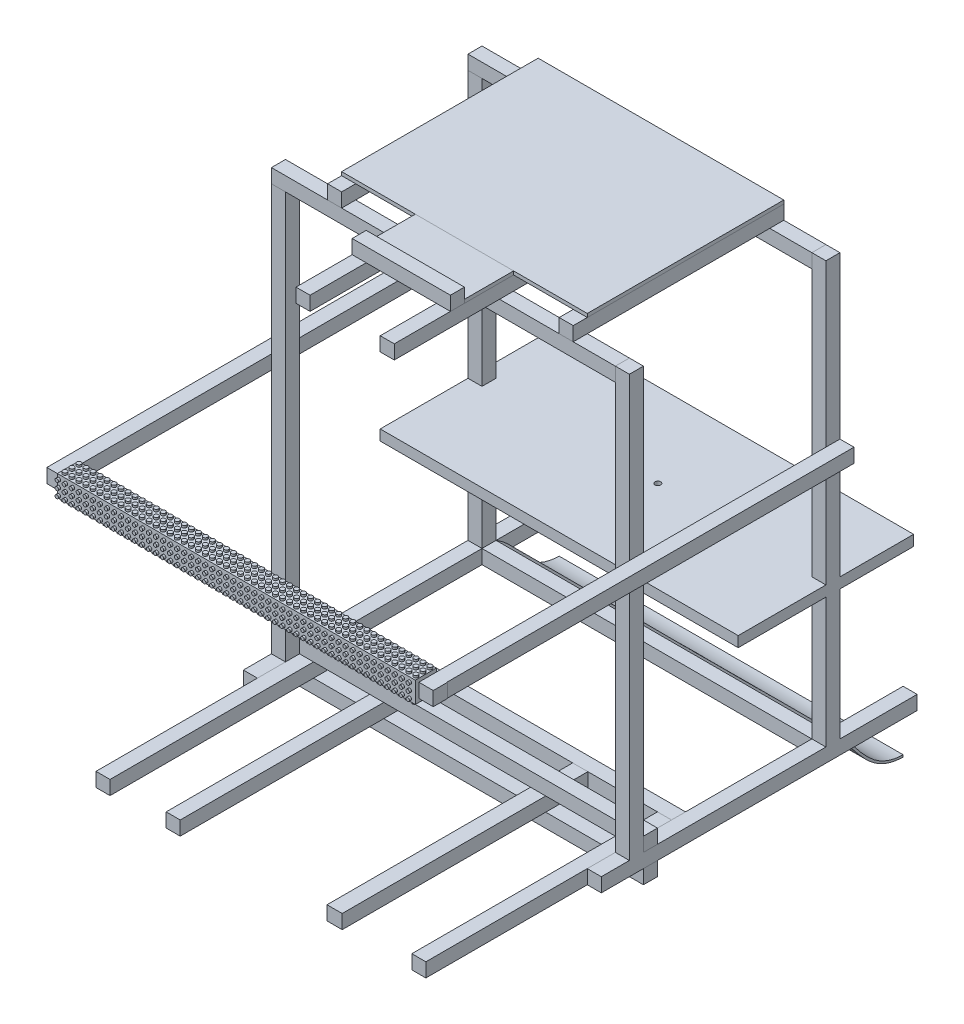
SolidWorks part; units mm, degrees
note: The reader was unsure of these and kept them because the rebuilt part matched: shared geometry of "Sketch11<3>".
ref_plane "Front Plane" through (0, 0, 0) normal (0, 0, 1) x (1, 0, 0)
ref_plane "Top Plane" through (0, 0, 0) normal (0, 1, 0) x (1, 0, 0)
ref_plane "Right Plane" through (0, 0, 0) normal (1, 0, 0) x (0, 0, -1)
sketch "Sketch1" plane through (0, 0, 0) normal (0, 0, 1) x (1, 0, 0)
  line L1 (-10, 10) -> (10, 10)
  line L2 (-10, 10) -> (-10, -10)
  line L3 (-10, -10) -> (10, -10)
  line L4 (10, 10) -> (10, -10)
  line L5 (-10, 10) -> (10, -10) construction
  line L6 (-10, -10) -> (10, 10) construction
  line L7 (480, 10) -> (500, 10)
  line L8 (480, 10) -> (480, -10)
  line L9 (480, -10) -> (500, -10)
  line L10 (500, 10) -> (500, -10)
  line L11 (480, 10) -> (500, -10) construction
  line L12 (480, -10) -> (500, 10) construction
  point P0 (0, 0)
  point P6 (490, 0)
  dimension "D1" = 20
  dimension "D2" = 20
  dimension "D3" = 20
  dimension "D4" = 20
  dimension "D5" = 490
extrude "Boss-Extrude1" add sketch "Sketch1" along normal blind 450
sketch "Sketch3" plane through (0, 10, 0) normal (0, 1, 0) x (1, 0, 0)
  line L0 (-10, -450) -> (10, -450) construction
  line L1 (-10, -450) -> (-10, 0) construction
  line L2 (10, -410) -> (-10, -410)
  line L3 (10, -410) -> (10, -390)
  line L4 (10, -390) -> (-10, -390)
  line L5 (-10, -410) -> (-10, -390)
  line L6 (10, -410) -> (-10, -390) construction
  line L7 (10, -390) -> (-10, -410) construction
  line L8 (10, -130) -> (-10, -130)
  line L9 (10, -130) -> (10, -110)
  line L10 (10, -110) -> (-10, -110)
  line L11 (-10, -130) -> (-10, -110)
  line L12 (10, -130) -> (-10, -110) construction
  line L13 (10, -110) -> (-10, -130) construction
  point P0 (0, -400)
  point P1 (0, -450)
  point P4 (0, -400)
  point P9 (0, -120)
  point P10 (0, -120)
  dimension "D1" = 50
  dimension "D2" = 20
  dimension "D3" = 20
  dimension "D4" = 120
  dimension "D5" = 20
  dimension "D6" = 20
extrude "Boss-Extrude2" add sketch "Sketch3" along normal blind 600 separate body
sketch "Sketch4" plane through (0, 0, 0) normal (0, 1, 0) x (1, 0, 0)
  line L0 (245, -471.4978) -> (245, 30.4512) construction
sketch "Sketch5" plane through (0, 10, 0) normal (0, 1, 0) x (1, 0, 0)
  line L0 (500, 0) -> (480, 0) construction
  line L1 (500, -450) -> (480, -450) construction
  line L2 (480, -450) -> (480, 0) construction
  line L3 (500, -410) -> (480, -410)
  line L4 (500, -410) -> (500, -390)
  line L5 (500, -390) -> (480, -390)
  line L6 (480, -410) -> (480, -390)
  line L7 (500, -410) -> (480, -390) construction
  line L8 (500, -390) -> (480, -410) construction
  line L9 (500, -130) -> (480, -130)
  line L10 (500, -130) -> (500, -110)
  line L11 (500, -110) -> (480, -110)
  line L12 (480, -130) -> (480, -110)
  line L13 (500, -130) -> (480, -110) construction
  line L14 (500, -110) -> (480, -130) construction
  point P0 (490, -400)
  point P1 (490, -120)
  point P5 (490, -450)
  point P8 (490, 0)
  point P9 (490, -400)
  point P14 (490, -120)
  dimension "D1" = 50
  dimension "D2" = 120
  dimension "D3" = 20
  dimension "D4" = 20
  dimension "D5" = 20
  dimension "D6" = 20
extrude "Boss-Extrude3" add sketch "Sketch5" along normal blind 600
sketch "Sketch6" plane through (480, 0, 0) normal (-1, 0, 0) x (0, 0, 1)
  line L0 (471.4978, 0) -> (-30.4512, 0) construction
  line L1 (0, 10) -> (0, -10) construction
  line L2 (450, -10) -> (0, -10) construction
  line L3 (310, 10) -> (330, 10)
  line L4 (310, 10) -> (310, -10)
  line L5 (310, -10) -> (330, -10)
  line L6 (330, 10) -> (330, -10)
  line L7 (310, 10) -> (330, -10) construction
  line L8 (310, -10) -> (330, 10) construction
  point P0 (320, 0)
  point P1 (0, 0)
  point P6 (320, 0)
  dimension "D1" = 320
  dimension "D2" = 20
  dimension "D3" = 20
extrude "Boss-Extrude4" add sketch "Sketch6" along normal blind 470 separate body
sketch "Sketch7" plane through (0, 0, 330) normal (0, 0, 1) x (1, 0, 0)
  line L0 (10, -10) -> (480, -10) construction
  line L4 (480, -10) -> (460, -10)
  line L5 (480, -10) -> (480, 10)
  line L6 (480, 10) -> (460, 10)
  line L7 (460, -10) -> (460, 10)
  line L8 (339.2062, 10) -> (360.7938, 10)
  line L9 (339.2062, 10) -> (339.2062, -10)
  line L10 (339.2062, -10) -> (360.7938, -10)
  line L11 (360.7938, 10) -> (360.7938, -10)
  line L12 (339.2062, 10) -> (360.7938, -10) construction
  line L13 (339.2062, -10) -> (360.7938, 10) construction
  line L14 (480, -10) -> (460, 10) construction
  line L15 (480, 10) -> (460, -10) construction
  line L16 (130, -10) -> (110, -10)
  line L17 (130, -10) -> (130, 10)
  line L18 (130, 10) -> (110, 10)
  line L19 (110, -10) -> (110, 10)
  line L20 (130, -10) -> (110, 10) construction
  line L21 (130, 10) -> (110, -10) construction
  line L22 (10, -10) -> (30, -10)
  line L23 (10, -10) -> (10, 10)
  line L24 (10, 10) -> (30, 10)
  line L25 (30, -10) -> (30, 10)
  line L26 (10, -10) -> (30, 10) construction
  line L27 (10, 10) -> (30, -10) construction
  point P0 (120, 0)
  point P1 (350, 0)
  point P2 (120, 0)
  point P3 (470, 0)
  point P4 (20, 0)
  point P9 (350, 0)
  point P19 (470, 0)
  point P24 (120, 0)
  point P29 (20, 0)
  dimension "D1" = 120
  dimension "D2" = 230
  dimension "D5" = 20
  dimension "D6" = 20
  dimension "D7" = 20
  dimension "D8" = 20
  dimension "D9" = 20
  dimension "D10" = 20
extrude "Boss-Extrude5" add sketch "Sketch7" along normal blind 350 separate body
sketch "Sketch8" plane through (480, 0, 0) normal (-1, 0, 0) x (0, 0, 1)
  line L0 (471.4978, 0) -> (-30.4512, 0) construction
  line L2 (110, 10) -> (130, 10)
  line L3 (110, 10) -> (110, -10)
  line L4 (110, -10) -> (130, -10)
  line L5 (130, 10) -> (130, -10)
  line L6 (110, 10) -> (130, -10) construction
  line L7 (110, -10) -> (130, 10) construction
  point P0 (120, 0)
  point P1 (120, 0)
  dimension "D1" = 120
  dimension "D2" = 20
  dimension "D3" = 20
extrude "Boss-Extrude6" add sketch "Sketch8" along normal blind 470 separate body
sketch "Sketch9" plane through (0, 0, 0) normal (1, 0, 0) x (0, 0, -1)
  line L0 (-471.4978, 0) -> (30.4512, 0) construction
  line L1 (-450, -10) -> (0, -10) construction
  line L2 (-390, 10) -> (-370, 10)
  line L3 (-390, 10) -> (-390, 30)
  line L4 (-390, 30) -> (-370, 30)
  line L5 (-370, 10) -> (-370, 30)
  line L6 (-390, 10) -> (-370, 30) construction
  line L7 (-390, 30) -> (-370, 10) construction
  line L8 (-370, -30) -> (-390, -30)
  line L9 (-370, -30) -> (-370, -10)
  line L10 (-370, -10) -> (-390, -10)
  line L11 (-390, -30) -> (-390, -10)
  line L12 (-370, -30) -> (-390, -10) construction
  line L13 (-370, -10) -> (-390, -30) construction
  point P0 (-380, 0)
  point P1 (-380, 20)
  point P5 (-380, -20)
  point P6 (-380, 20)
  point P11 (-380, -20)
  dimension "D1" = 380
  dimension "D2" = 20
  dimension "D3" = 20
  dimension "D4" = 20
  dimension "D5" = 20
  dimension "D6" = 20
  dimension "D7" = 20
extrude "Boss-Extrude7" add sketch "Sketch9" along normal blind 500 and the other way blind 10 separate body
sketch "Sketch10" plane through (480, 0, 0) normal (-1, 0, 0) x (0, 0, 1)
  line L0 (410, 610) -> (410, 10) construction
  line L1 (390, 610) -> (410, 610)
  line L2 (390, 610) -> (390, 590)
  line L3 (390, 590) -> (410, 590)
  line L4 (410, 610) -> (410, 590)
  line L5 (130, 610) -> (130, 10) construction
  line L6 (110, 610) -> (130, 610)
  line L7 (110, 610) -> (110, 590)
  line L8 (110, 590) -> (130, 590)
  line L9 (130, 610) -> (130, 590)
  line M6 (410, 10) -> (410, 610)
  line M7 (410, 610) -> (390, 610)
  line M8 (390, 610) -> (390, 10)
extrude "Boss-Extrude9" add sketch "Sketch10" along direction (-1, 0, 0) on the side of the normal up to surface (490 mm away) separate body contours L3 M8 M6 M7 | L9 L6 L7 L8
sketch "Sketch11" plane through (0, 0, 110) normal (0, 0, -1) x (-1, 0, 0)
  line L0 (10, 610) -> (-480, 610) construction
  line L1 (-70, 610) -> (-90, 610)
  line L2 (-70, 610) -> (-70, 630)
  line L3 (-70, 630) -> (-90, 630)
  line L4 (-90, 610) -> (-90, 630)
  line L5 (-480, 610) -> (-480, 590) construction
  line L6 (-400, 610) -> (-420, 610)
  line L7 (-400, 610) -> (-400, 630)
  line L8 (-400, 630) -> (-420, 630)
  line L9 (-420, 610) -> (-420, 630)
  line L10 (10, 590) -> (10, 610) construction
  line L11 (-480, 610) -> (-480, 10) construction
  line L12 (-315, 610) -> (-295, 610)
  line L13 (-315, 610) -> (-315, 630)
  line L14 (-315, 630) -> (-295, 630)
  line L15 (-295, 610) -> (-295, 630)
  line L16 (-175, 610) -> (-195, 610)
  line L17 (-175, 610) -> (-175, 630)
  line L18 (-175, 630) -> (-195, 630)
  line L19 (-195, 610) -> (-195, 630)
  point P10 (-480, 600)
  line M14 (10, 610) -> (-480, 610)
  dimension "D1" = 60
  dimension "D2" = 80
  dimension "D3" = 20
  dimension "D4" = 20
  dimension "D5" = 165
  dimension "D6" = 20
  dimension "D7" = 100
  dimension "D8" = 20
extrude "Boss-Extrude10" add sketch "Sketch11" against normal up to surface (300 mm away) separate body contours L4 L2 L3 M14 | L9 L7 L8 M14 up to face at (235, 600, 410)
extrude "Boss-Extrude11" add sketch "Sketch11<3>" against normal offset from surface (450 mm away) 150 separate body contours L15 L14 L13 M14 | L19 L17 L18 M14 up to face at (235, 600, 410) offset beyond the face yes
sketch "Sketch11<3>" plane through (0, 0, 110) normal (0, 0, -1) x (-1, 0, 0) same geometry as "Sketch11"
sketch "Sketch12" plane through (315, 0, 0) normal (1, 0, 0) x (0, 0, -1)
  line L0 (-560, 630) -> (-110, 630) construction
  line L1 (-460, 630) -> (-480, 630)
  line L2 (-460, 630) -> (-460, 650)
  line L3 (-460, 650) -> (-480, 650)
  line L4 (-480, 630) -> (-480, 650)
  line L5 (-410, 610) -> (-410, 10) construction
  dimension "D1" = 50
extrude "Boss-Extrude12" add sketch "Sketch12" against normal up to surface (140 mm away) separate body up to face at (175, 620, 335)
sketch "Sketch13" plane through (0, 0, 110) normal (0, 0, -1) x (-1, 0, 0)
  line L0 (10, 610) -> (10, 10) construction
  line L1 (10, 380) -> (30, 380)
  line L2 (10, 380) -> (10, 360)
  line L3 (10, 360) -> (30, 360)
  line L4 (30, 380) -> (30, 360)
  line L5 (-500, 610) -> (-500, 10) construction
  line L6 (-500, 360) -> (-520, 360)
  line L7 (-500, 360) -> (-500, 380)
  line L8 (-500, 380) -> (-520, 380)
  line L9 (-520, 360) -> (-520, 380)
  line L11 (-10, 10) -> (-480, 10) construction
  line L12 (-10, 10) -> (-480, 10) construction
  dimension "D1" = 350
  dimension "D2" = 350
  dimension "D3" = 20
  dimension "D4" = 20
  dimension "D5" = 20
extrude "Boss-Extrude13" add sketch "Sketch13" against normal offset from surface (600 mm away) 300 separate body up to face at (0, 310, 410) offset beyond the face yes
sketch "Sketch14" plane through (175, 0, 0) normal (-1, 0, 0) x (0, 0, 1)
  line L1 (460, 630) -> (390, 630)
  line L2 (460, 630) -> (460, 635)
  line L3 (460, 635) -> (390, 635)
  line L4 (390, 630) -> (390, 635)
extrude "Boss-Extrude14" add sketch "Sketch14" against normal up to surface (140 mm away) separate body up to face at (315, 620, 335)
sketch "Sketch16" plane through (0, 0, 110) normal (0, 0, -1) x (-1, 0, 0)
  line L1 (-70, 630) -> (-420, 630)
  line L2 (-70, 630) -> (-70, 635)
  line L3 (-70, 635) -> (-420, 635)
  line L4 (-420, 630) -> (-420, 635)
extrude "Boss-Extrude15" add sketch "Sketch16" against normal up to surface (280 mm away) separate body up to face at (245, 632.5, 390)
sketch "Sketch18" plane through (-10, 0, 0) normal (-1, 0, 0) x (0, 0, 1)
  line L0 (110, 10) -> (110, -10) construction
  line L1 (450, 10) -> (0, 10) construction
  circle A0 centre (30, -4.6) radius 5
  dimension "D1" = 80
  dimension "D2" = 14.6
extrude "Cut-Extrude1" cut sketch "Sketch18" against normal up to next (20 mm away)
ref_plane "Plane1" through (-10, 10, 110) normal (0, 0, 1) x (1, 0, 0)
sketch "Sketch21" plane through (-10, 0, 0) normal (-1, 0, 0) x (0, 0, 1)
  line L0 (110, 4.5) -> (110, 15.5) construction
  line L1 (450, 10) -> (0, 10) construction
  line L2 (450, -10) -> (0, -10) construction
  line L3 (0, -74.5) -> (0.0648, -77.4993)
  line L4 (110, 10) -> (111.5076, 7.4063)
  spline S0 degree 3 poles (110, 10) (68.4606, -14.1454) (56.9133, -73.2706) (0, -74.5) knots 0 0 0 0 1 1 1 1
  spline S1 degree 1 poles (111.5076, 7.4063) (0.0648, -77.4993) knots 0 0 1 1 construction
  spline S2 degree 3 poles (111.5076, 7.4063) (109.0293, 5.9658) (104.2323, 2.7841) (95.4025, -4.4673) (85.4048, -14.9775) (74.2925, -28.8562) (63.2026, -42.9306) (53.224, -53.9138) (44.3201, -61.6853) (37.0629, -66.8533) (29.1159, -71.2014) (21.8383, -74.0053) (15.5818, -75.6786) (10.6643, -76.6306) (6.3651, -77.1573) (2.8127, -77.4102) (0.9762, -77.4796) (0.0648, -77.4993) knots 0 0 0 0 0.0625 0.125 0.25 0.375 0.5 0.625 0.6875 0.75 0.8125 0.875 0.90625 0.9375 0.96875 0.984375 1 1 1 1
  dimension "D1" = 64.5
  dimension "D2" = 3
extrude "Boss-Extrude17" add sketch "Sketch21" against normal up to surface (490 mm away) up to face at (480, 256.6667, 265.4167)
sketch "Sketch23" plane through (500, 0, 0) normal (1, 0, 0) x (0, 0, -1)
  line L0 (-390, 10) -> (-130, 10) construction
  line L1 (-255, 210) -> (-5, 210)
  line L2 (-255, 210) -> (-255, 195)
  line L3 (-255, 195) -> (-5, 195)
  line L4 (-5, 210) -> (-5, 195)
  line L5 (-130, 610) -> (-130, 10) construction
  dimension "D1" = 250
  dimension "D2" = 15
  dimension "D3" = 200
  dimension "D4" = 125
extrude "Boss-Extrude18" add sketch "Sketch23" against normal up to surface (510 mm away)
sketch "Sketch24" plane through (0, 210, 0) normal (0, 1, 0) x (1, 0, 0)
  line L0 (500, -130) -> (500, -255) construction
  circle A0 centre (255, -124.3629) radius 4
  dimension "D1" = 245
extrude "Cut-Extrude2" cut sketch "Sketch24" against normal up to next (15 mm away)
sketch "Sketch25" plane through (0, 380, 0) normal (0, 1, 0) x (1, 0, 0)
  line L0 (-30, -710) -> (-30, -110) construction
  line L1 (-30, -690) -> (520.537, -690)
  line L2 (-30, -690) -> (-30, -710)
  line L3 (-30, -710) -> (520.537, -710)
  line L4 (520.537, -690) -> (520.537, -710)
  dimension "D1" = 20
extrude "Boss-Extrude19" add sketch "Sketch25" against normal up to surface (20 mm away) up to face at (-20, 360, 410)
sketch "Sketch26" plane through (-10, 0, 0) normal (1, 0, 0) x (0, 0, -1)
  line L1 (-690, 360) -> (-710, 360)
  line L2 (-690, 360) -> (-690, 380)
  line L3 (-690, 380) -> (-710, 380)
  line L4 (-710, 360) -> (-710, 380)
  line L5 (-685, 355) -> (-715, 355)
  line L6 (-685, 355) -> (-685, 385)
  line L7 (-685, 385) -> (-715, 385)
  line L8 (-715, 355) -> (-715, 385)
  dimension "D1" = 5
  dimension "D2" = 5
  dimension "D3" = 5
  dimension "D4" = 5
extrude "Boss-Extrude20" add sketch "Sketch26" along normal up to surface (510 mm away) up to face at (500, 370, 400)
sketch "Sketch27" plane through (0, 355, 0) normal (0, -1, 0) x (1, 0, 0)
  circle A0 centre (-6.6888, 710.0204) radius 2.3129
extrude "Boss-Extrude21" add sketch "Sketch27" along normal blind 4
pattern_linear "LPattern1" count 51 spacing 10 along (1, 0, 0) count 3 spacing 10 along (0, 0, -1) of "Boss-Extrude21"
sketch "Sketch28" plane through (0, 0, 715) normal (0, 0, 1) x (1, 0, 0)
  circle A0 centre (492.1096, 378.8603) radius 2.4569
extrude "Boss-Extrude22" add sketch "Sketch28" along normal blind 3
pattern_linear "LPattern2" count 51 spacing 10 along (-1, 0, 0) count 3 spacing 10 along (0, -1, 0) of "Boss-Extrude22"
sketch "Sketch29" plane through (0, 385, 0) normal (0, 1, 0) x (1, 0, 0)
  circle A0 centre (495.6054, -689.7524) radius 3.0577
extrude "Boss-Extrude23" add sketch "Sketch29" along normal blind 3
pattern_linear "LPattern3" count 51 spacing 10 along (-1, 0, 0) count 3 spacing 10 along (0, 0, 1) of "Boss-Extrude23"
